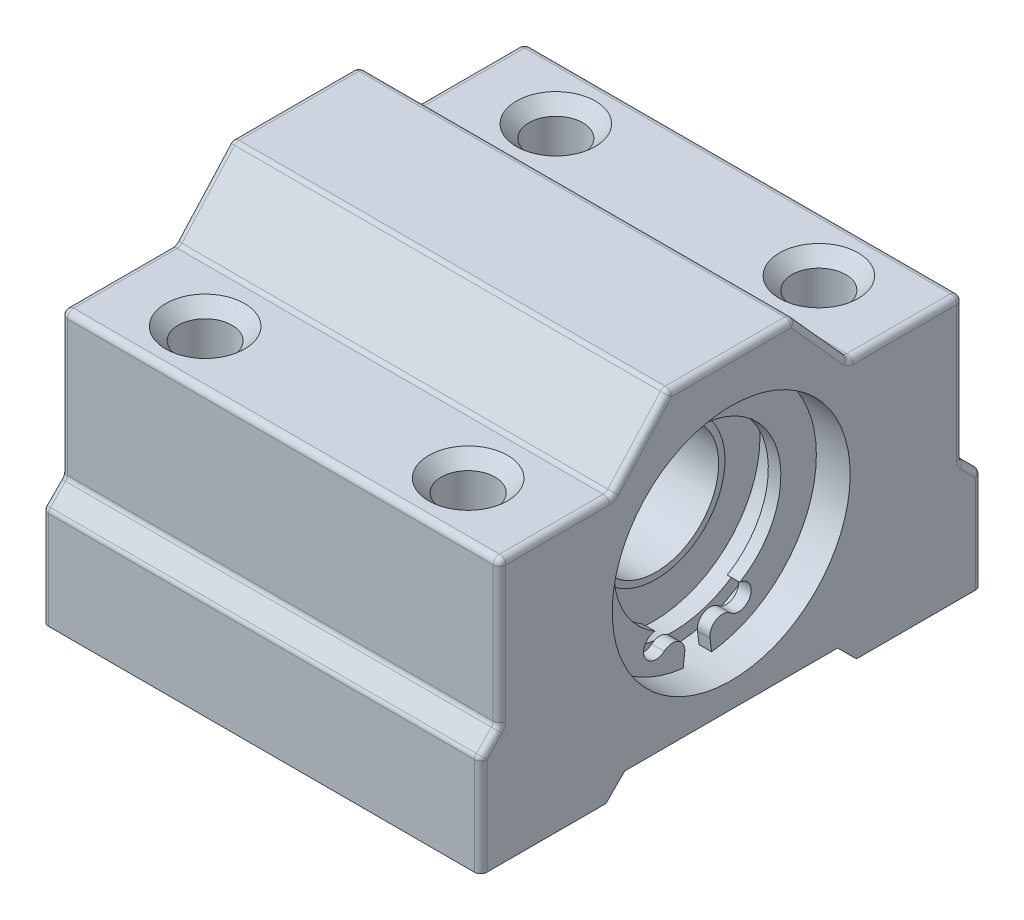
SolidWorks part; units mm, degrees
ref_plane "Front Plane" through (0, 0, 0) normal (0, 0, 1) x (1, 0, 0)
ref_plane "Top Plane" through (0, 0, 0) normal (0, 1, 0) x (1, 0, 0)
ref_plane "Right Plane" through (0, 0, 0) normal (1, 0, 0) x (0, 0, -1)
sketch "Sketch1" plane through (0, 0, 0) normal (1, 0, 0) x (0, 0, -1)
  line L1 (-10, -13) -> (-8.5, -11.5)
  line L2 (-8.5, -11.5) -> (8.5, -11.5)
  line L3 (8.5, -11.5) -> (10, -13)
  line L4 (10, -13) -> (20, -13)
  line L6 (20, -5) -> (18.5, -3.5)
  line L8 (18.5, 8) -> (9.5, 8)
  line L9 (9.5, 8) -> (5, 13)
  line L10 (5, 13) -> (-5, 13)
  line L11 (-5, 13) -> (-9.5, 8)
  line L12 (-9.5, 8) -> (-18.5, 8)
  line L15 (-20, -5) -> (-20, -13)
  line L16 (0, -11.5) -> (0, 13) construction
  line L17 (-16.278, 0) -> (14.0247, 0) construction
  line L18 (-20, -13) -> (-10, -13)
  line L19 (20, -5) -> (20, -13)
  line L20 (-18.5, -3.5) -> (-18.5, 8)
  line L21 (18.5, -3.5) -> (18.5, 8)
  line L22 (-14, 8) -> (-14, -13) construction
  line L23 (-14, -13) -> (14, 8) construction
  line L24 (14, 8) -> (14, -13) construction
  line L25 (-20, -5) -> (-18.5, -3.5)
  line L26 (-9.5, 0) -> (9.5, 0) construction
  circle A0 centre (0, 0) radius 9.5
  circle A1 centre (0, 0) radius 8.5
  circle A2 centre (0, 0) radius 5
  point P18 (0, 13)
  dimension "D12" = 10
  dimension "D1" = 40
  dimension "D2" = 21
  dimension "D3" = 13
  dimension "D5" = 26
  dimension "D6" = 28
  dimension "D4" = 8
  dimension "D7" = 1.5
  dimension "D8" = 10
  dimension "D9" = 1.5
  dimension "D10" = 10
  dimension "D11" = 1
extrude "Boss-Extrude1" add sketch "Sketch1" along normal blind 35 contours L25 L15 L18 L1 L2 L3 L4 L19 L6 L21 L8 L9 L10 L11 L12 L20 A0 region at (0, -12.5229, 15)
extrude "Extrude-Thin1" add sketch "Sketch1<4>" along normal blind 28.5 from offset 0.5 separate body thin contours A2 thin type one direction wall 0.5
sketch "Sketch1<4>" plane through (0, 0, 0) normal (1, 0, 0) x (0, 0, -1) same geometry as "Sketch1"
extrude "Boss-Extrude2" add sketch "Sketch1<5>" along normal blind 28 from offset 0.8 contours A1 A2 region at (0, 0, 8.2596)
sketch "Sketch1<5>" plane through (0, 0, 0) normal (1, 0, 0) x (0, 0, -1) same geometry as "Sketch1"
extrude "Boss-Extrude3" add sketch "Sketch1<6>" along normal blind 30 from offset 0.3 contours A0 A1 region at (0, 0, 9.2313)
sketch "Sketch1<6>" plane through (0, 0, 0) normal (1, 0, 0) x (0, 0, -1) same geometry as "Sketch1"
ref_plane "Plane1" through (30.3, 0, 0) normal (1, 0, 0) x (0, 0, -1)
sketch "Sketch3" plane through (30.3, 0, 0) normal (1, 0, 0) x (0, 0, -1)
  line L0 (0, 0) -> (0, -50000) construction
  line L1 (-1.0159, -8.4391) -> (-1.1354, -9.4319)
  line L2 (1.0159, -8.4391) -> (1.1354, -9.4319)
  circle A0 centre (0, 0) radius 9.5 construction
  arc A1 (1.1354, -9.4319) -> (-1.1354, -9.4319) centre (0, 0) ccw
  circle A2 centre (0, 0) radius 8.5 construction
  arc A3 (0, -8.5) -> (1.0159, -8.4391) centre (0, 0) ccw
  arc A4 (-1.0159, -8.4391) -> (-2.6476, -7.4994) centre (-2, -8.2614) ccw
  circle A5 centre (-2, -8.2614) radius 0.25
  arc A6 (-2.2421, -8.199) -> (-1.7562, -8.3166) centre (0, 0) ccw
  arc A7 (-2.6476, -7.4994) -> (-3.3869, -5.7416) centre (-3.2952, -6.7374) cw
  arc A8 (2.6476, -7.4994) -> (3.3869, -5.7416) centre (3.2952, -6.7374) ccw
  circle A10 centre (2, -8.2614) radius 0.25
  arc A11 (1.0159, -8.4391) -> (2.6476, -7.4994) centre (2, -8.2614) cw
  arc A13 (3.3869, -5.7416) -> (-3.3869, -5.7416) centre (0, 0) ccw
  dimension "D1" = 0.5
  dimension "D2" = 2
  dimension "D3" = 1
  dimension "D4" = 2
extrude "Boss-Extrude4" add sketch "Sketch3" along normal blind 1 from offset 1 contours A11 A8 A13 A7 A4 L1 A1 L2
fillet "Fillet1" radius 0.5 32 edges at (17.5, -3.5, -18.5) (17.5, -3.5, 18.5) (17.5, -5, 20) (17.5, -5, -20) (17.5, 8, -9.5) (17.5, 8, 9.5) (17.5, 13, 5) (17.5, 13, -5) (17.5, 8, -18.5) (17.5, 8, 18.5) (35, 10.5, -7.25) (35, 10.5, 7.25) (35, 2.25, 18.5) (0, -4.25, 19.25) (0, 10.5, 7.25) (35, -4.25, -19.25) (35, -9, -20) (35, 2.25, -18.5) (35, 13, 0) (35, 8, -14) (35, 8, 14) (35, -4.25, 19.25) (35, -9, 20) (0, -9, -20) (0, -4.25, -19.25) (0, 2.25, -18.5) (0, 10.5, -7.25) (0, 8, -14) (0, 13, 0) (0, -9, 20) (0, 2.25, 18.5) (0, 8, 14)
sketch "Sketch4" plane through (0, -13, 0) normal (0, -1, 0) x (1, 0, 0)
  line L0 (17.5, 20) -> (17.5, -20) construction
  line L1 (34.5, 20) -> (0.5, 20) construction
  line L2 (34.5, -20) -> (0.5, -20) construction
  line L4 (-4.9444, 14) -> (27.0918, 14) construction
  line L6 (0, 0) -> (36.1646, 0) construction
  circle A0 centre (7, 14) radius 2.15
  circle A1 centre (28, 14) radius 2.15
  circle A2 centre (28, -14) radius 2.15
  circle A3 centre (7, -14) radius 2.15
  dimension "D2" = 4.3
  dimension "D1" = 14
  dimension "D3" = 21
extrude "Cut-Extrude3" cut sketch "Sketch4" against normal through all
chamfer "Chamfer1" distance 1 angle 45 6 edges at (28, 8, -16.15) (7, 8, -16.15) (7, 8, 11.85) (28, 8, 11.85) (28, -13, 16.15) (7, -13, 11.85)
equation "\"D1@Boss-Extrude2\"= \"D1@Boss-Extrude1\" - 2 - 5"
equation "\"D1@Boss-Extrude3\"= \"D1@Boss-Extrude1\" - 5"
equation "\"D1@Sketch4\"= \"D6@Sketch1\" / 2"
equation "\"D1@Extrude-Thin1\"= \"D1@Boss-Extrude3\" - 1.5"
